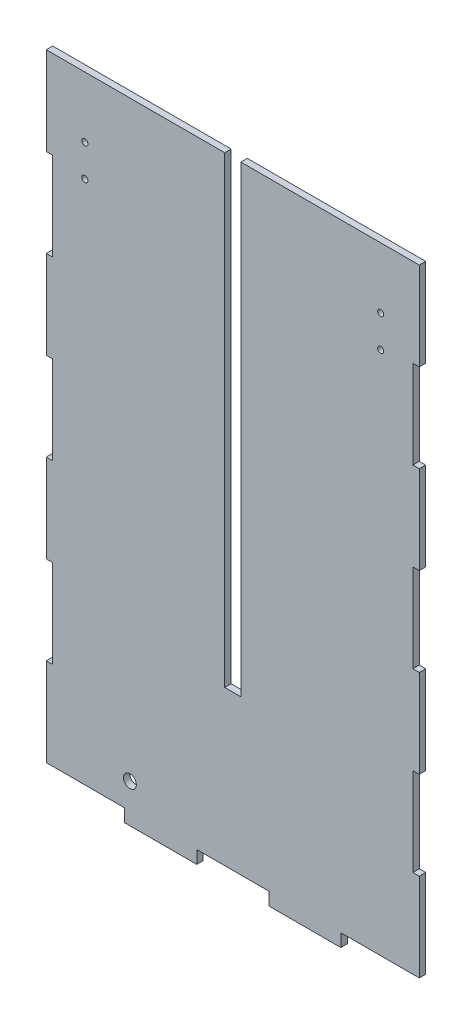
SolidWorks part; units mm, degrees
ref_plane "Front Plane" through (0, 0, 0) normal (0, 0, 1) x (1, 0, 0)
ref_plane "Top Plane" through (0, 0, 0) normal (0, 1, 0) x (1, 0, 0)
ref_plane "Right Plane" through (0, 0, 0) normal (1, 0, 0) x (0, 0, -1)
sketch "Sketch2" plane through (0, 0, 0) normal (0, 0, 1) x (1, 0, 0)
  line L0 (0, 152.4) -> (0, -152.4) construction
  line L1 (-88.9, 152.4) -> (88.9, 152.4)
  line L2 (-88.9, 152.4) -> (-88.9, -152.4)
  line L3 (-88.9, -152.4) -> (88.9, -152.4)
  line L4 (88.9, 152.4) -> (88.9, -152.4)
  line L5 (-88.9, 108.8571) -> (-88.9, 65.3143)
  line L6 (-88.9, 152.4) -> (-92.075, 152.4)
  line L7 (-88.9, 152.4) -> (-88.9, 108.8571)
  line L8 (-88.9, 108.8571) -> (-92.075, 108.8571)
  line L9 (-92.075, 152.4) -> (-92.075, 108.8571)
  line L10 (88.9, 152.4) -> (92.075, 152.4)
  line L11 (88.9, 152.4) -> (88.9, 108.8571)
  line L12 (88.9, 108.8571) -> (92.075, 108.8571)
  line L13 (92.075, 152.4) -> (92.075, 108.8571)
  line L18 (-88.9, 108.8571) -> (-92.075, 108.8571)
  line L19 (-92.075, 108.8571) -> (-92.075, 65.3143)
  line L20 (-88.9, 65.3143) -> (-92.075, 65.3143)
  line L21 (88.9, 108.8571) -> (88.9, 65.3143)
  line L22 (88.9, 108.8571) -> (92.075, 108.8571)
  line L23 (92.075, 108.8571) -> (92.075, 65.3143)
  line L24 (88.9, 65.3143) -> (92.075, 65.3143)
  line L25 (-88.9, 65.3143) -> (-88.9, 21.7714)
  line L26 (-88.9, 65.3143) -> (-92.075, 65.3143)
  line L27 (-92.075, 65.3143) -> (-92.075, 21.7714)
  line L28 (-88.9, 21.7714) -> (-92.075, 21.7714)
  line L29 (88.9, 65.3143) -> (88.9, 21.7714)
  line L30 (88.9, 65.3143) -> (92.075, 65.3143)
  line L31 (92.075, 65.3143) -> (92.075, 21.7714)
  line L32 (88.9, 21.7714) -> (92.075, 21.7714)
  line L33 (-88.9, 21.7714) -> (-88.9, -21.7714)
  line L34 (-88.9, 21.7714) -> (-92.075, 21.7714)
  line L35 (-92.075, 21.7714) -> (-92.075, -21.7714)
  line L36 (-88.9, -21.7714) -> (-92.075, -21.7714)
  line L37 (88.9, 21.7714) -> (88.9, -21.7714)
  line L38 (88.9, 21.7714) -> (92.075, 21.7714)
  line L39 (92.075, 21.7714) -> (92.075, -21.7714)
  line L40 (88.9, -21.7714) -> (92.075, -21.7714)
  line L41 (-88.9, -21.7714) -> (-88.9, -65.3143)
  line L42 (-88.9, -21.7714) -> (-92.075, -21.7714)
  line L43 (-92.075, -21.7714) -> (-92.075, -65.3143)
  line L44 (-88.9, -65.3143) -> (-92.075, -65.3143)
  line L45 (88.9, -21.7714) -> (88.9, -65.3143)
  line L46 (88.9, -21.7714) -> (92.075, -21.7714)
  line L47 (92.075, -21.7714) -> (92.075, -65.3143)
  line L48 (88.9, -65.3143) -> (92.075, -65.3143)
  line L49 (-88.9, -65.3143) -> (-88.9, -108.8571)
  line L50 (-88.9, -65.3143) -> (-92.075, -65.3143)
  line L51 (-92.075, -65.3143) -> (-92.075, -108.8571)
  line L52 (-88.9, -108.8571) -> (-92.075, -108.8571)
  line L53 (88.9, -65.3143) -> (88.9, -108.8571)
  line L54 (88.9, -65.3143) -> (92.075, -65.3143)
  line L55 (92.075, -65.3143) -> (92.075, -108.8571)
  line L56 (88.9, -108.8571) -> (92.075, -108.8571)
  line L57 (-88.9, -108.8571) -> (-88.9, -152.4)
  line L58 (-88.9, -108.8571) -> (-92.075, -108.8571)
  line L59 (-92.075, -108.8571) -> (-92.075, -152.4)
  line L60 (-88.9, -152.4) -> (-92.075, -152.4)
  line L61 (88.9, -108.8571) -> (88.9, -152.4)
  line L62 (88.9, -108.8571) -> (92.075, -108.8571)
  line L63 (92.075, -108.8571) -> (92.075, -152.4)
  line L64 (88.9, -152.4) -> (92.075, -152.4)
  line L89 (-88.9, -152.4) -> (-88.9, -158.75)
  line L90 (-88.9, -158.75) -> (-53.34, -158.75)
  line L91 (-53.34, -158.75) -> (-53.34, -152.4)
  line L92 (-53.34, -152.4) -> (-88.9, -152.4)
  line L93 (-53.34, -152.4) -> (-53.34, -158.75)
  line L94 (-53.34, -158.75) -> (-17.78, -158.75)
  line L95 (-17.78, -158.75) -> (-17.78, -152.4)
  line L96 (-17.78, -152.4) -> (-53.34, -152.4)
  line L97 (-17.78, -152.4) -> (-17.78, -158.75)
  line L98 (-17.78, -158.75) -> (17.78, -158.75)
  line L99 (17.78, -158.75) -> (17.78, -152.4)
  line L100 (17.78, -152.4) -> (-17.78, -152.4)
  line L101 (17.78, -152.4) -> (17.78, -158.75)
  line L102 (17.78, -158.75) -> (53.34, -158.75)
  line L103 (53.34, -158.75) -> (53.34, -152.4)
  line L104 (53.34, -152.4) -> (17.78, -152.4)
  line L105 (53.34, -152.4) -> (53.34, -158.75)
  line L106 (53.34, -158.75) -> (88.9, -158.75)
  line L107 (88.9, -158.75) -> (88.9, -152.4)
  line L108 (88.9, -152.4) -> (53.34, -152.4)
  line L109 (-88.9, -152.4) -> (-53.34, -152.4) construction
  point P6 (0, 0)
  dimension "D1" = 177.8
  dimension "D2" = 184.15
  dimension "D3" = 304.8
  dimension "D6" = 43.5429
  dimension "D4" = 6.35
  dimension "D8" = 35.56
  dimension "D9" = 35.56
  dimension "D5" = 7
  dimension "D7" = 5
extrude "Boss-Extrude1" add sketch "Sketch2" along normal blind 3.175 contours L4 L1 L2 L3 | L94 L95 L3 L91 | L102 L103 L3 L99 | L60 L2 L52 L59 | L44 L2 L36 L43 | L28 L2 L20 L27 | L6 L9 L8 L2 | L13 L10 L4 L12 | L4 L32 L31 L24 | L4 L48 L47 L40 | L4 L64 L63 L56 region at (0, 0, 0) region at (-90.4875, 130.6286, 0) region at (90.4875, 130.6286, 0) region at (-90.4875, 43.5429, 0) region at (90.4875, 43.5429, 0) region at (-90.4875, -43.5429, 0) region at (90.4875, -43.5429, 0) region at (-90.4875, -130.6286, 0) region at (90.4875, -130.6286, 0) region at (-35.56, -155.575, 0) region at (35.56, -155.575, 0)
sketch "Sketch3" plane through (0, 0, 3.175) normal (0, 0, 1) x (1, 0, 0)
  line L0 (-92.075, 152.4) -> (92.075, 152.4) construction
  line L1 (-3.9688, 152.4) -> (3.9687, 152.4)
  line L2 (-3.9688, 152.4) -> (-3.9687, -76.2)
  line L3 (-3.9687, -76.2) -> (3.9688, -76.2)
  line L4 (3.9687, 152.4) -> (3.9688, -76.2)
  line L5 (0, -76.2) -> (0, 0) construction
  dimension "D1" = 7.9375
  dimension "D2" = 228.6
extrude "Cut-Extrude1" cut sketch "Sketch3" against normal through all
sketch "Sketch4" plane through (0, 0, 3.175) normal (0, 0, 1) x (1, 0, 0)
  line L2 (-88.9, -65.3143) -> (-88.9, -108.8571) construction
  line L3 (-92.075, -152.4) -> (-53.34, -152.4) construction
  circle A0 centre (-50.8, -139.7) radius 3.175
  dimension "D1" = 6.35
  dimension "D2" = 12.7
  dimension "D3" = 38.1
extrude "Cut-Extrude2" cut sketch "Sketch4" against normal through all
sketch "Sketch5" plane through (0, 0, 3.175) normal (0, 0, 1) x (1, 0, 0)
  line L1 (-92.075, 152.4) -> (-3.9688, 152.4) construction
  line L2 (0, -152.4) -> (0, 152.4) construction
  line L3 (-17.78, -152.4) -> (17.78, -152.4) construction
  line L4 (-92.075, 152.4) -> (-92.075, 108.8571) construction
  circle A0 centre (-73.025, 122.4) radius 1.5
  circle A1 centre (-73.025, 106.65) radius 1.5
  circle A2 centre (73.025, 122.4) radius 1.5
  circle A3 centre (73.025, 106.65) radius 1.5
  dimension "D1" = 3
  dimension "D2" = 3
  dimension "D3" = 15.75
  dimension "D4" = 19.05
  dimension "D5" = 30
extrude "Cut-Extrude3" cut sketch "Sketch5" against normal up to surface (3.175 mm away) up to face at (-47.625, -139.7, 0)
equation "\"Height\"= 12in"
equation "\"Depth\"= 7in"
equation "\"WallThickness\"= 0.125in"
equation "\"FloorThickness\"= 0.25in"
equation "\"D1@Sketch2\"=\"Depth\""
equation "\"D2@Sketch2\"=\"D1@Sketch2\"+2*\"WallThickness\""
equation "\"D3@Sketch2\"=\"Height\""
equation "\"D6@Sketch2\"=\"D3@Sketch2\"/\"D5@Sketch2\""
equation "\"D1@Boss-Extrude1\"=\"WallThickness\""
equation "\"Width\" = 30in"
equation "\"D4@Sketch2\"=\"FloorThickness\""
equation "\"D9@Sketch2\"=\"D1@Sketch2\"/\"D7@Sketch2\""
equation "\"D8@Sketch2\"=\"D9@Sketch2\""
